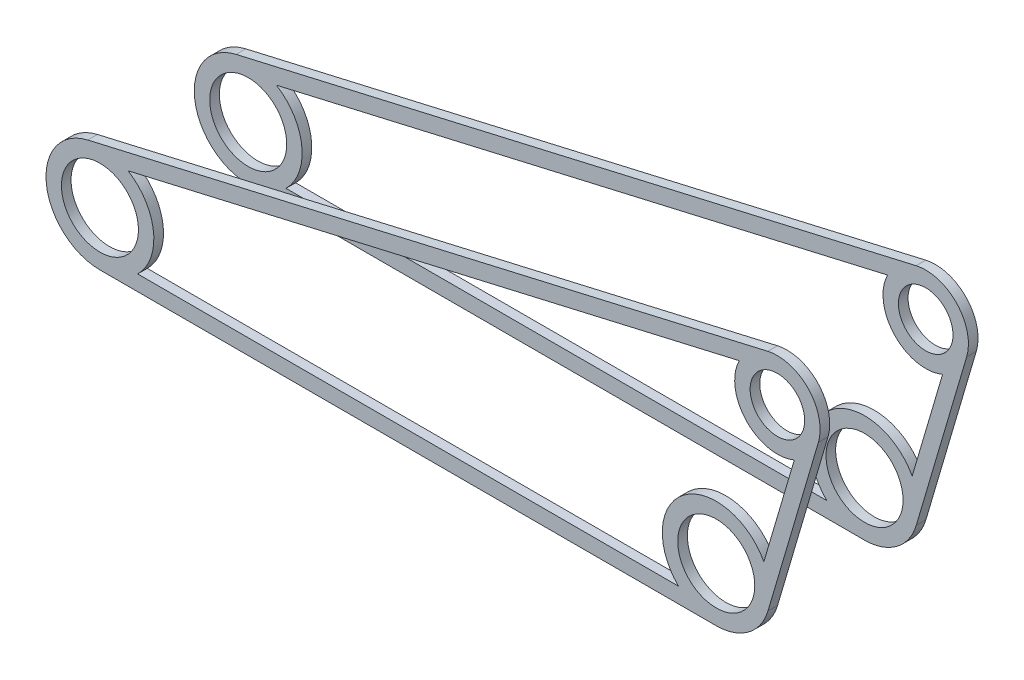
SolidWorks part; units mm, degrees
material "AISI 4130 Steel, annealed at 865C"
ref_plane "Front Plane" through (0, 0, 0) normal (0, 0, 1) x (1, 0, 0)
ref_plane "Top Plane" through (0, 0, 0) normal (0, 1, 0) x (1, 0, 0)
ref_plane "Right Plane" through (0, 0, 0) normal (1, 0, 0) x (0, 0, -1)
sketch "Sketch1" plane through (0, 0, 0) normal (0, 0, 1) x (1, 0, 0)
  line L0 (0, 0) -> (101.6, 0) construction
  line L1 (101.6, 0) -> (111.6816, 27.6855) construction
  line L2 (111.6816, 27.6855) -> (0, 0) construction
  line L3 (-2, 8.6621) -> (110.0977, 34.5451)
  line L4 (118.4348, 25.6968) -> (110.1279, -2.5114)
  line L5 (101.6, -8.89) -> (0, -8.89)
  line L6 (-1.4286, 6.1872) -> (110.6692, 32.0702)
  line L7 (0, -6.35) -> (101.6, -6.35)
  line L8 (107.6914, -1.7938) -> (115.9983, 26.4143)
  circle A0 centre (0, 0) radius 6.35
  circle A1 centre (101.6, 0) radius 6.35
  circle A2 centre (111.6816, 27.6855) radius 4.5
  circle A3 centre (0, 0) radius 8.89
  circle A4 centre (101.6, 0) radius 8.89
  circle A5 centre (111.6816, 27.6855) radius 7.04
  dimension "D1" = 9
  dimension "D2" = 12.7
  dimension "D3" = 12.7
  dimension "D6" = 2.54
  dimension "D7" = 2.54
  dimension "D8" = 2.54
  dimension "D4" = 101.6
  dimension "D5" = 29.464
  dimension "D9" = 115.062
extrude "Boss-Extrude1" add sketch "Sketch1" along normal blind 1.5875 from offset 11.43 contours A5 L3 A3 L6 | L6 A3 L7 A0 | A4 L7 A3 L5 | L7 A4 L8 A1 | A5 L8 A4 L4 | A5 L6 A2 L8 | L7 A3 L6 A0 | L8 A4 L7 A1 | L6 A5 L8 A2 region at (1.3849, 8.5452, 0) region at (54.5812, 20.4415, 0) region at (115.9459, 33.0467, 0) region at (50.8, -7.6421, 0) region at (7.602, 4.2648, 0) region at (108.0678, 31.3042, 0) region at (98.3154, -8.0456, 0) region at (113.2192, 12.1635, 0) region at (96.4108, 6.9376, 0)
extrude "Boss-Extrude2" add sketch "Sketch1<4>" against normal blind 1.5875 from offset 11.43 separate body contours A5 L3 A3 L6 | L6 A3 L7 A0 | L7 A3 L6 A0 | A4 L7 A3 L5 | L7 A4 L8 A1 | L8 A4 L7 A1 | A5 L8 A4 L4 | L6 A5 L8 A2 | A5 L6 A2 L8 region at (1.3849, 8.5452, 0) region at (54.5812, 20.4415, 0) region at (115.9459, 33.0467, 0) region at (50.8, -7.6421, 0) region at (7.602, 4.2648, 0) region at (108.0678, 31.3042, 0) region at (98.3154, -8.0456, 0) region at (113.2192, 12.1635, 0) region at (96.4108, 6.9376, 0) offset against normal yes
sketch "Sketch1<4>" plane through (0, 0, 0) normal (0, 0, 1) x (1, 0, 0) same geometry as "Sketch1"
equation "\"D19@Boss-Extrude2\"=.45"
